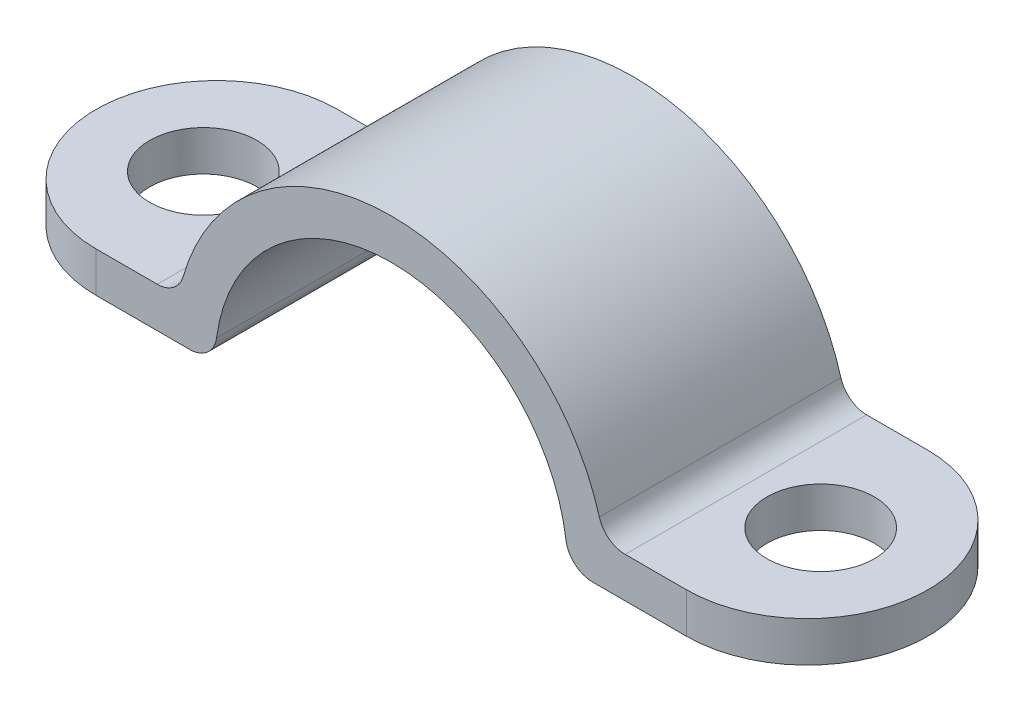
SolidWorks part; units mm, degrees
ref_plane "Front Plane" through (0, 0, 0) normal (0, 0, 1) x (1, 0, 0)
ref_plane "Top Plane" through (0, 0, 0) normal (0, 1, 0) x (1, 0, 0)
ref_plane "Right Plane" through (0, 0, 0) normal (1, 0, 0) x (0, 0, -1)
sketch "Sketch1" plane through (0, 0, 0) normal (0, 0, 1) x (1, 0, 0)
  line L0 (-17.4429, 0) -> (31, 0) construction
  line L1 (31, 0) -> (15, 0)
  line L2 (-15, 0) -> (-31, 0)
  line L3 (31, 3) -> (17.4298, 3)
  line L4 (-17.4298, 3) -> (-31, 3)
  line L5 (-31, 0) -> (-31, 3)
  line L6 (31, 0) -> (31, 3)
  line L7 (-15.8514, 3) -> (-31, 3) construction
  line L8 (31, 3) -> (15.8514, 3) construction
  line L9 (31, 0) -> (13.1327, 0) construction
  line L10 (-13.1327, 0) -> (-31, 0) construction
  arc A0 (13.0175, 1.7357) -> (-13.0175, 1.7357) centre (0, 0) ccw
  arc A1 (15.5073, 4.4485) -> (-15.5073, 4.4485) centre (0, 0) ccw
  arc A2 (15.8514, 3) -> (-15.8514, 3) centre (0, 0) ccw construction
  arc A3 (-15.5073, 4.4485) -> (-17.4298, 3) centre (-17.4298, 5) cw
  arc A4 (17.4298, 3) -> (15.5073, 4.4485) centre (17.4298, 5) cw
  arc A5 (13.1327, 0) -> (-13.1327, 0) centre (0, 0) ccw construction
  arc A6 (15, 0) -> (13.0175, 1.7357) centre (15, 2) cw
  arc A7 (-15, 0) -> (-13.0175, 1.7357) centre (-15, 2) ccw
  point P21 (13.1327, 0)
  dimension "D1" = 62
  dimension "D4" = 2
  dimension "D2" = 3
  dimension "D3" = 16
extrude "Boss-Extrude1" add sketch "Sketch1" along normal blind 18 contours A1 A3 L4 L5 L2 A7 A0 A6 L1 L6 L3 A4
sketch "Sketch2" plane through (0, 3, 0) normal (0, 1, 0) x (1, 0, 0)
  line L0 (31, -9) -> (-35.1735, -9) construction
  line L1 (31, -18) -> (31, 0) construction
  line L2 (23, 0) -> (23, -24.6147) construction
  circle A0 centre (-23, -9) radius 4
  circle A1 centre (23, -9) radius 4
  point P6 (0, 0)
  point P14 (0, 0)
  point P15 (0, 0)
  dimension "D1" = 8
  dimension "D2" = 23
  dimension "D3" = 23
extrude "Cut-Extrude1" cut sketch "Sketch2" against normal up to next
fillet "Fillet2" 2 edges at (-31, 1.5, 0) (-31, 1.5, 18) type full round first side face at (0, 3.8384, 0) second side face at (0, 3.8384, 18) middle face at (-31, 1.5, 9)
fillet "Fillet3" 2 edges at (31, 1.5, 18) (31, 1.5, 0) type full round first side face at (1.5, 3.8384, 18) second side face at (1.5, 3.8384, 0) middle face at (31, 1.5, 9)
